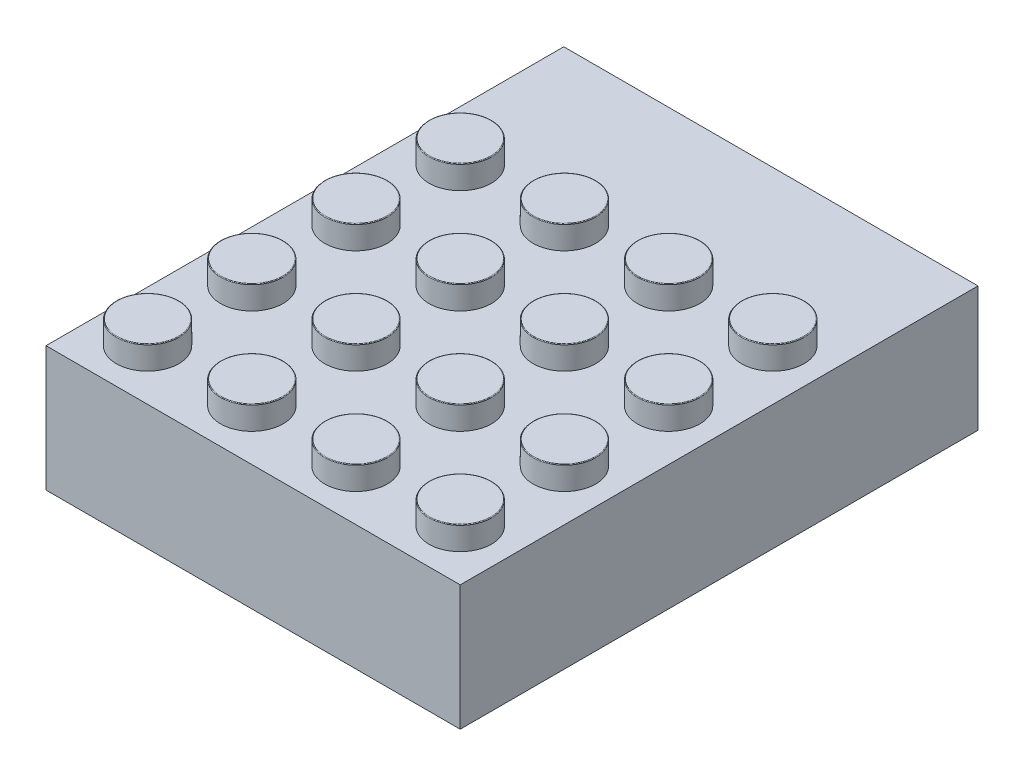
SolidWorks part; units mm, degrees
ref_plane "Front Plane" through (0, 0, 0) normal (0, 0, 1) x (1, 0, 0)
ref_plane "Top Plane" through (0, 0, 0) normal (0, 1, 0) x (1, 0, 0)
ref_plane "Right Plane" through (0, 0, 0) normal (1, 0, 0) x (0, 0, -1)
sketch "Sketch1" plane through (0, 0, 0) normal (0, 1, 0) x (1, 0, 0)
  line L1 (-15.9, -19.875) -> (15.9, -19.875)
  line L2 (-15.9, -19.875) -> (-15.9, 19.875)
  line L3 (-15.9, 19.875) -> (15.9, 19.875)
  line L4 (15.9, -19.875) -> (15.9, 19.875)
  line L5 (-15.9, -19.875) -> (15.9, 19.875) construction
  line L6 (-15.9, 19.875) -> (15.9, -19.875) construction
  point P0 (0, 0)
  dimension "D1" = 31.8
  dimension "D2" = 39.75
extrude "Boss-Extrude1" add sketch "Sketch1" along normal blind 9.6
sketch "Sketch2" plane through (0, 9.6, 0) normal (0, 1, 0) x (1, 0, 0)
  line L0 (-15.9, -19.875) -> (15.9, -19.875) construction
  line L1 (-15.9, 19.875) -> (-15.9, -19.875) construction
  circle A0 centre (-12, -15.975) radius 2.4
  dimension "D1" = 4.8
  dimension "D2" = 3.9
  dimension "D3" = 3.9
extrude "Boss-Extrude2" add sketch "Sketch2" along normal blind 1.8
pattern_linear "LPattern1" count 4 spacing 8 along (0, 0, -1) of "Boss-Extrude2"
pattern_linear "LPattern2" count 4 spacing 8 along (1, 0, 0) of "LPattern1"
fillet "Fillet1" radius 0.05 16 edges at (-12, 11.4, 18.375) (12, 11.4, 18.375) (-4, 11.4, -5.625) (4, 11.4, -5.625) (12, 11.4, -5.625) (12, 11.4, 2.375) (4, 11.4, 2.375) (-4, 11.4, 2.375) (4, 11.4, 18.375) (-4, 11.4, 18.375) (-4, 11.4, 10.375) (4, 11.4, 10.375) (12, 11.4, 10.375) (-12, 11.4, -5.625) (-12, 11.4, 2.375) (-12, 11.4, 10.375)
sketch "Sketch3" plane through (0, 0, 0) normal (0, -1, 0) x (-1, 0, 0)
  line L0 (15.9, 19.875) -> (15.9, -19.875) construction
  line L1 (-14.7, 18.675) -> (14.7, 18.675)
  line L2 (-14.7, 18.675) -> (-14.7, -18.675)
  line L3 (-14.7, -18.675) -> (14.7, -18.675)
  line L4 (14.7, 18.675) -> (14.7, -18.675)
  line L5 (-14.7, 18.675) -> (14.7, -18.675) construction
  line L6 (-14.7, -18.675) -> (14.7, 18.675) construction
  line L7 (15.9, -19.875) -> (-15.9, -19.875) construction
  point P0 (0, 0)
  dimension "D1" = 1.2
  dimension "D2" = 1.2
extrude "Cut-Extrude1" cut sketch "Sketch3" against normal blind 6.8
sketch "Sketch4" plane through (0, 6.8, 0) normal (0, -1, 0) x (-1, 0, 0)
  circle A0 centre (-8, 4.025) radius 3.2125
  circle A2 centre (-12, 0.025) radius 2.4 construction
  circle A3 centre (-12, 8.025) radius 2.4 construction
  dimension "D1" = 6.425
  dimension "D3" = 4
  dimension "D2" = 4
extrude "Boss-Extrude3" add sketch "Sketch4" along normal up to surface (6.8 mm away) up to face at (0, 0, 0)
sketch "Sketch5" plane through (0, 0, 0) normal (0, -1, 0) x (-1, 0, 0)
  circle A0 centre (-8, 4.025) radius 2.25
  circle A1 centre (-8, 4.025) radius 3.2125 construction
  dimension "D1" = 4.5
extrude "Cut-Extrude2" cut sketch "Sketch5" against normal up to surface (6.8 mm away) up to face at (8, 6.8, -7.2375)
pattern_linear "LPattern3" count 3 spacing 8 along (-1, 0, 0) of "Cut-Extrude2", "Boss-Extrude3"
pattern_linear "LPattern4" count 3 spacing 8 along (0, 0, 1) of "LPattern3"
pattern_linear "LPattern5" count 2 spacing 8 along (0, 0, -1) of "LPattern3"
ref_axis "Axis1" through (0, 0, 0) along (0, 1, 0)
sketch "Sketch6" plane through (0, 0, 0) normal (0, -1, 0) x (-1, 0, 0)
  line L0 (14.7, -18.675) -> (14.7, 18.675) construction
  line L1 (14.7, -16.275) -> (14.4, -16.275)
  line L2 (14.7, -16.275) -> (14.7, -15.675)
  line L3 (14.7, -15.675) -> (14.4, -15.675)
  line L4 (14.4, -16.275) -> (14.4, -15.675)
  line L5 (14.7, -18.675) -> (14.7, 18.675) construction
  line L6 (14.7, -8.275) -> (14.4, -8.275)
  line L7 (14.7, -8.275) -> (14.7, -7.675)
  line L8 (14.7, -7.675) -> (14.4, -7.675)
  line L9 (14.4, -8.275) -> (14.4, -7.675)
  line L10 (15.9, -19.875) -> (-15.9, -19.875) construction
  line L11 (14.7, -0.275) -> (14.4, -0.275)
  line L12 (14.7, -0.275) -> (14.7, 0.325)
  line L13 (14.7, 0.325) -> (14.4, 0.325)
  line L14 (14.4, -0.275) -> (14.4, 0.325)
  line L15 (14.7, 15.675) -> (14.4, 15.675)
  line L16 (14.7, 15.675) -> (14.7, 16.275)
  line L17 (14.7, 16.275) -> (14.4, 16.275)
  line L18 (14.4, 15.675) -> (14.4, 16.275)
  line L19 (-15.9, 19.875) -> (15.9, 19.875) construction
  line L20 (14.7, 7.725) -> (14.4, 7.725)
  line L21 (14.7, 7.725) -> (14.7, 8.325)
  line L22 (14.7, 8.325) -> (14.4, 8.325)
  line L23 (14.4, 7.725) -> (14.4, 8.325)
  point P20 (14.7, -15.975)
  point P23 (14.7, 15.975)
  point P31 (0, 0)
  point P32 (0, 0)
  dimension "D1" = 0.3
  dimension "D2" = 0.6
  dimension "D3" = 0.6
  dimension "D4" = 0.6
  dimension "D5" = 0.6
  dimension "D6" = 3.9
  dimension "D9" = 3.9
  dimension "D7" = 8
  dimension "D8" = 8
  dimension "D10" = 0.6
  dimension "D11" = 8
extrude "Boss-Extrude4" add sketch "Sketch6" against normal up to surface (6.8 mm away) up to face at (-8, 6.8, -15.2375)
mirror "Mirror1" about plane through (0, 0, 0) normal (1, 0, 0) of "Boss-Extrude4"
sketch "Sketch7" plane through (0, 0, 0) normal (0, -1, 0) x (1, 0, 0)
  line L0 (14.7, 18.675) -> (-14.7, 18.675) construction
  line L1 (-12.3, 18.675) -> (-11.7, 18.675)
  line L2 (-12.3, 18.675) -> (-12.3, 18.375)
  line L3 (-12.3, 18.375) -> (-11.7, 18.375)
  line L4 (-11.7, 18.675) -> (-11.7, 18.375)
  line L5 (-14.7, 18.675) -> (-14.7, 16.275) construction
  line L6 (-4.3, 18.675) -> (-3.7, 18.675)
  line L7 (-4.3, 18.675) -> (-4.3, 18.375)
  line L8 (-4.3, 18.375) -> (-3.7, 18.375)
  line L9 (-3.7, 18.675) -> (-3.7, 18.375)
  line L10 (3.7, 18.675) -> (4.3, 18.675)
  line L11 (3.7, 18.675) -> (3.7, 18.375)
  line L12 (3.7, 18.375) -> (4.3, 18.375)
  line L13 (4.3, 18.675) -> (4.3, 18.375)
  line L15 (11.7, 18.675) -> (12.3, 18.675)
  line L16 (11.7, 18.675) -> (11.7, 18.375)
  line L17 (11.7, 18.375) -> (12.3, 18.375)
  line L18 (12.3, 18.675) -> (12.3, 18.375)
  dimension "D1" = 0.3
  dimension "D2" = 0.6
  dimension "D3" = 0.6
  dimension "D4" = 0.6
  dimension "D8" = 8
  dimension "D5" = 8
  dimension "D6" = 8
  dimension "D7" = 2.4
  dimension "D9" = 0.6
extrude "Boss-Extrude5" add sketch "Sketch7" against normal up to next
mirror "Mirror2" about plane through (0, 0, 0) normal (0, 0, 1) of "Boss-Extrude5"
equation "\"D2@Sketch1\"=\"D1@Sketch1\"*1.25"
equation "\"D3@Sketch2\"=\"D2@Sketch2\""
equation "\"D2@Sketch3\"=\"D1@Sketch3\""
equation "\"D3@Sketch6\"=\"D2@Sketch6\""
equation "\"D4@Sketch6\"=\"D3@Sketch6\""
equation "\"D5@Sketch6\"=\"D4@Sketch6\""
equation "\"D3@Sketch7\"=\"D2@Sketch7\""
equation "\"D4@Sketch7\"=\"D3@Sketch7\""
equation "\"D7@Sketch7\"=2.4"
equation "\"D9@Sketch7\"=\"D4@Sketch7\""
